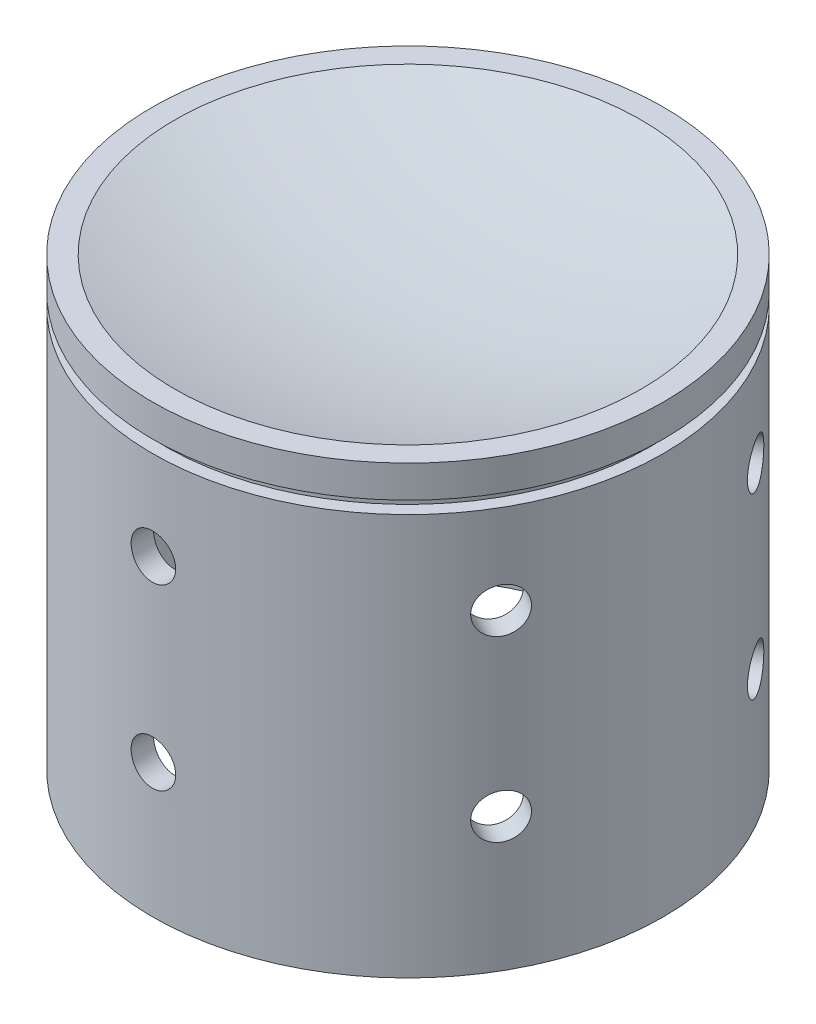
SolidWorks part; units mm, degrees
material "6061-T6 (SS)"
ref_plane "Front Plane" through (0, 0, 0) normal (0, 0, 1) x (1, 0, 0)
ref_plane "Top Plane" through (0, 0, 0) normal (0, 1, 0) x (1, 0, 0)
ref_plane "Right Plane" through (0, 0, 0) normal (1, 0, 0) x (0, 0, -1)
sketch "Sketch1" plane through (0, 0, 0) normal (0, 0, 1) x (1, 0, 0)
  line L0 (0, -25.4) -> (38.0365, -25.4)
  line L1 (0, 0) -> (38.0365, 0)
  line L2 (0, 0) -> (0, -63.5)
  line L3 (0, -63.5) -> (38.0365, -63.5)
  line L4 (38.0365, 0) -> (38.0365, -63.5)
  line L5 (36.3855, -25.4) -> (36.3855, 0)
  line L6 (0, -14.4216) -> (0, 22.2823) construction
  line L7 (33.2105, 0) -> (33.2105, -25.4)
  line L8 (36.3855, -25.4) -> (36.3855, -63.5)
  line L9 (0, 0) -> (0, -5.08)
  line L10 (0, -5.08) -> (0, -10.16)
  line L11 (0, -10.16) -> (36.3855, -10.16)
  line L12 (36.3855, -10.16) -> (36.3855, 0)
  line L13 (33.2105, -25.4) -> (33.2105, -63.5)
  line L14 (36.3855, -4.572) -> (34.6075, -4.572)
  line L15 (36.3855, -4.572) -> (36.3855, -6.35)
  line L16 (36.3855, -6.35) -> (34.6075, -6.35)
  line L17 (34.6075, -4.572) -> (34.6075, -6.35)
  arc A0 (0, -5.08) -> (33.2105, 0) centre (0, 106.0168) ccw
  point P22 (35.4965, -6.35)
  dimension "D8" = 5.08
  dimension "D1" = 38.0365
  dimension "D2" = 63.5
  dimension "D3" = 25.4
  dimension "D4" = 1.651
  dimension "D5" = 3.175
  dimension "D6" = 4.572
  dimension "D7" = 5.08
  dimension "D9" = 1.778
  dimension "D10" = 1.778
ref_axis "Axis1" through (0, 0, 0) along (0, -1, 0)
revolve "Revolve2" add sketch "Sketch1" angle 360 about axis through (0, 0, 0) along (0, -1, 0) region at (34.798, -17.78, 0) region at (34.798, -44.45, 0) region at (18.6759, -6.6127, 0) region at (33.3169, -5.08, 0) reverse direction yes
hole_wizard "1/4 (0.25) Diameter Hole4" positions "3DSketch7" profile "Sketch8" hole size "1/4" standard "ANSI Inch" end condition through all
sketch3d "3DSketch7"
  point P3 (0, -19.05, 36.3855)
  point P14 (0, -44.45, 36.3855)
sketch "Sketch8" plane through (0, -19.05, 36.3855) normal (1, 0, 0) x (0, -1, 0)
  line L0 (0, 0) -> (0, 72.771)
  line L1 (0, 72.771) -> (3.175, 72.771)
  line L2 (3.175, 72.771) -> (3.175, 0)
  line L5 (3.175, 0) -> (0, 0)
  line L11 (0, -6.35) -> (0, 107.95) construction
  dimension "Thru Hole Dia." = 6.35
  dimension "Thru Hole Depth" = 72.771
pattern_circular "CirPattern2" count 6 every 60 about axis through (0, 0, 0) along (0, -1, 0) of "1/4 (0.25) Diameter Hole4"
